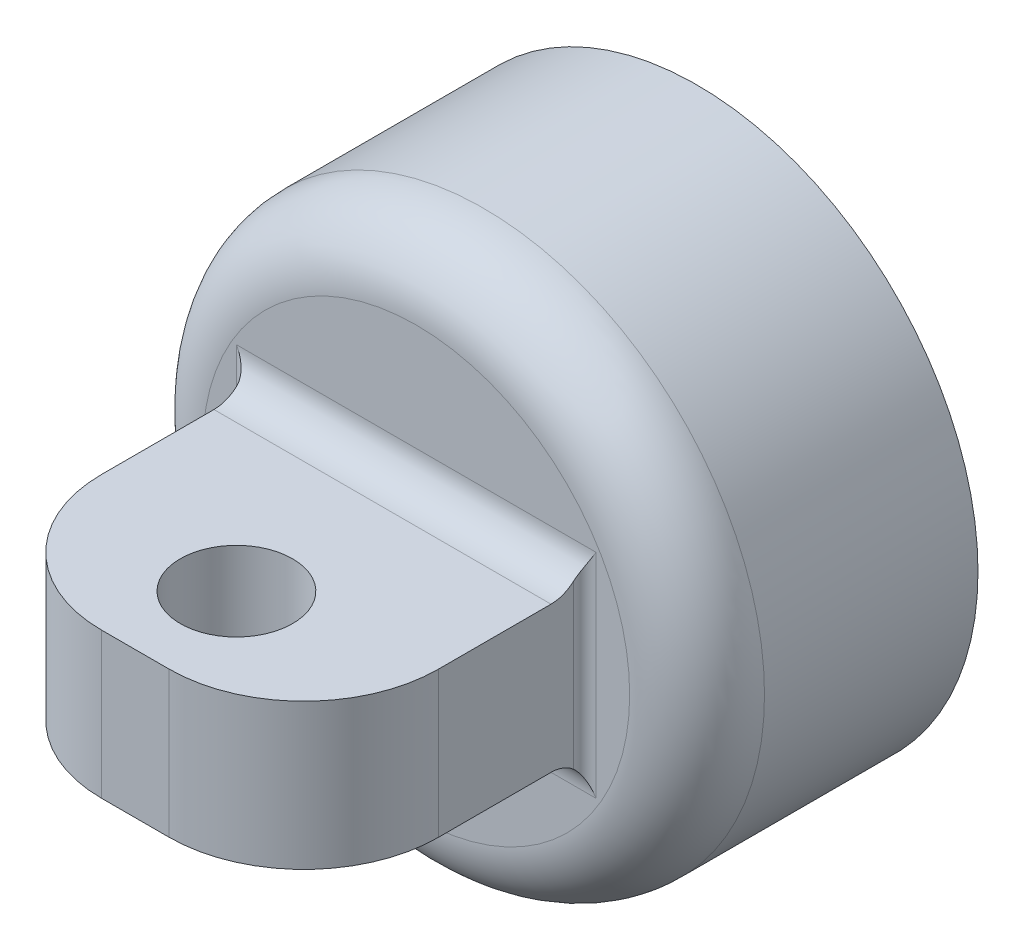
SolidWorks part; units mm, degrees
ref_plane "Front Plane" through (0, 0, 0) normal (0, 0, 1) x (1, 0, 0)
ref_plane "Top Plane" through (0, 0, 0) normal (0, 1, 0) x (1, 0, 0)
ref_plane "Right Plane" through (0, 0, 0) normal (1, 0, 0) x (0, 0, -1)
sketch "Sketch1" plane through (0, 0, 0) normal (0, 0, 1) x (1, 0, 0)
  circle A0 centre (0, 0) radius 25
  dimension "D1" = 50
extrude "Boss-Extrude1" add sketch "Sketch1" along normal blind 25
sketch "Sketch2" plane through (0, 0, 25) normal (0, 0, 1) x (1, 0, 0)
  line L1 (-15, -6.4821) -> (15, -6.4821)
  line L2 (-15, -6.4821) -> (-15, 6.4821)
  line L3 (-15, 6.4821) -> (15, 6.4821)
  line L4 (15, -6.4821) -> (15, 6.4821)
  line L5 (-15, -6.4821) -> (15, 6.4821) construction
  line L6 (-15, 6.4821) -> (15, -6.4821) construction
  point P0 (0, 0)
  dimension "D1" = 12.9642
  dimension "D2" = 30
extrude "Boss-Extrude2" add sketch "Sketch2" along normal blind 25
fillet "Fillet1" radius 12 2 edges at (15, 0, 50) (-15, 0, 50)
fillet "Fillet2" radius 1 2 edges at (15, 0, 25) (-15, 0, 25)
fillet "Fillet3" radius 3 2 edges at (0, 6.4821, 25) (0, -6.4821, 25)
sketch "Sketch3" plane through (0, -6.4821, 0) normal (0, -1, 0) x (1, 0, 0)
  line L0 (-3, 50) -> (3, 50) construction
  circle A0 centre (0, 41) radius 5
  dimension "D1" = 9
  dimension "D2" = 10
extrude "Cut-Extrude1" cut sketch "Sketch3" against normal up to surface (12.9642 mm away) up to face at (0, 6.4821, 39.4951)
fillet "Fillet4" radius 6 1 edges at (25, 0, 25)
